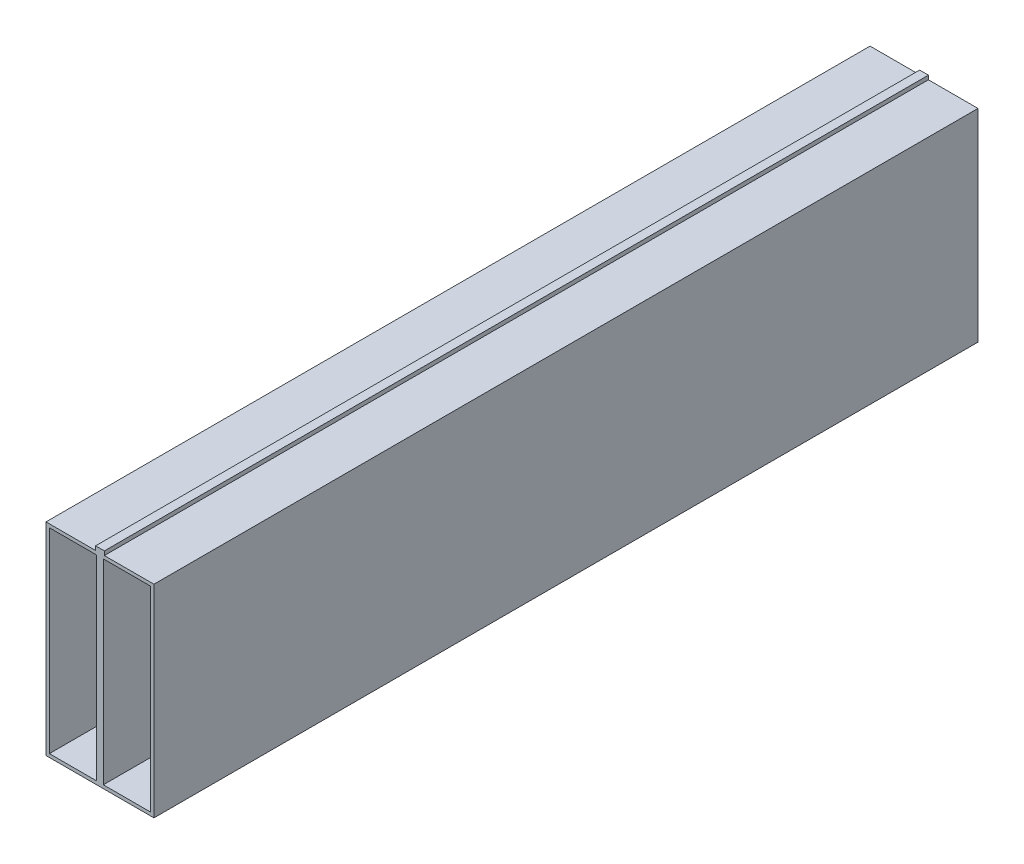
SolidWorks part; units mm, degrees
ref_plane "Plan de face" through (0, 0, 0) normal (0, 0, 1) x (1, 0, 0)
ref_plane "Plan de dessus" through (0, 0, 0) normal (0, 1, 0) x (1, 0, 0)
ref_plane "Plan de droite" through (0, 0, 0) normal (1, 0, 0) x (0, 0, -1)
sketch "Esquisse1" plane through (0, 0, 0) normal (0, 0, 1) x (1, 0, 0)
  line L0 (425, 1475) -> (425, 25)
  line L1 (0, 0) -> (800, 0)
  line L2 (0, 0) -> (0, 1500)
  line L3 (0, 1500) -> (800, 1500)
  line L4 (800, 0) -> (800, 1500)
  line L5 (25, 1475) -> (375, 1475)
  line L6 (25, 1475) -> (25, 25)
  line L7 (25, 25) -> (375, 25)
  line L8 (375, 1475) -> (375, 25)
  line L9 (425, 25) -> (775, 25)
  line L10 (775, 25) -> (775, 1475)
  line L11 (775, 1475) -> (425, 1475)
  line L12 (400, -1) -> (400, 1) construction
  point P16 (400, 0)
  dimension "D1" = 1500
  dimension "D2" = 800
  dimension "D3" = 25
  dimension "D4" = 25
  dimension "D5" = 25
  dimension "D6" = 25
  dimension "D7" = 25
  dimension "D8" = 25
  dimension "D9" = 25
  dimension "D10" = 25
extrude "Boss.-Extru.1" add sketch "Esquisse1" against normal blind 6000 and the other way blind 107.28
sketch "Esquisse2" plane through (0, 0, 107.28) normal (0, 0, 1) x (1, 0, 0)
  line L0 (400, 1500) -> (400, 1546.5728) construction
  line L1 (800, 1500) -> (0, 1500) construction
  line L2 (367.5, 1500) -> (432.5, 1500)
  line L3 (432.5, 1500) -> (432.5, 1530)
  line L4 (432.5, 1530) -> (367.5, 1530)
  line L5 (367.5, 1530) -> (367.5, 1500)
  point P7 (400, 1500)
  dimension "D1" = 65
  dimension "D2" = 30
extrude "Boss.-Extru.2" add sketch "Esquisse2" against normal up to surface (6107.28 mm away) up to face at (600, 750, -6000)
